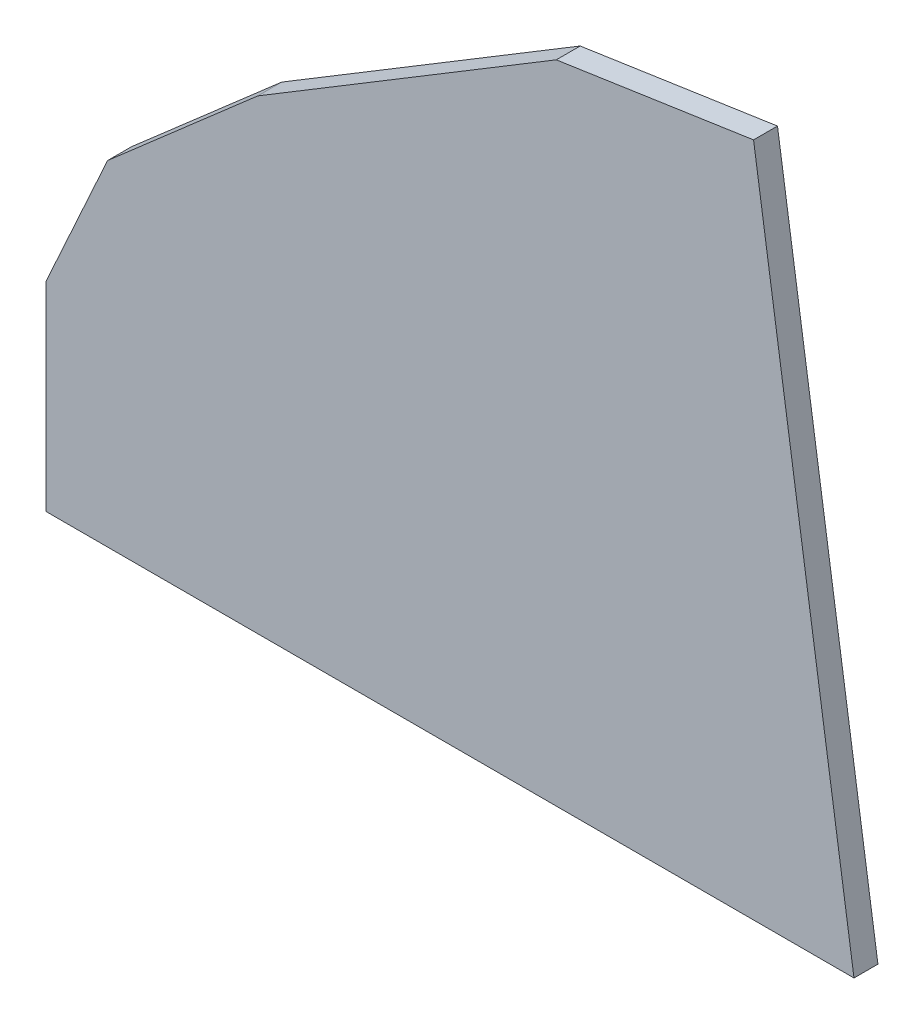
SolidWorks part; units mm, degrees
material "AISI 1020"
ref_plane "Спереди" through (0, 0, 0) normal (0, 0, 1) x (1, 0, 0)
ref_plane "Сверху" through (0, 0, 0) normal (0, 1, 0) x (1, 0, 0)
ref_plane "Справа" through (0, 0, 0) normal (1, 0, 0) x (0, 0, -1)
sketch "Эскиз1" plane through (0, 0, 0) normal (0, 0, 1) x (1, 0, 0)
  line L0 (-207.4146, 166.7802) -> (-245.0885, 133.9065)
  line L1 (-149.1432, 100) -> (-2208.4434, 2460) construction
  line L2 (-215.5022, 100) -> (-2274.8024, 2460) construction
  line L3 (-245.0885, 133.9065) -> (-260.5022, 100)
  line L4 (-115.9638, 100) -> (-4500, 100) construction
  line L5 (-260.5022, 100) -> (-260.5022, 50)
  line L7 (-260.5022, 50) -> (-57.9819, 50)
  line L11 (-57.9819, 50) -> (-83.157, 219.359)
  line L12 (-83.157, 219.359) -> (-132.6136, 212.0073)
  line L13 (-466.7768, 2460) -> (-101.0988, 0) construction
  line L14 (-132.6136, 212.0073) -> (-207.4146, 166.7802)
  line L15 (-245.0885, 133.9065) -> (-215.5022, 100) construction
  line L16 (-215.5022, 100) -> (-260.5022, 100) construction
  line L17 (-132.6136, 212.0073) -> (-115.9638, 100) construction
  line L18 (-115.9638, 100) -> (-207.4146, 166.7802) construction
  line L19 (-20.039, 10) -> (-20.039, 90) construction
  line L20 (-101.0988, 0) -> (-4500, 0) construction
  point P11 (-260.5022, 26.6646)
  point P14 (-73.606, 50)
  point P16 (-57.9819, 50)
  point P17 (0, 0)
  point P18 (-72.1263, 50)
  point P28 (-20.039, 50)
  point P29 (0, 0)
  point P30 (0, 0)
  point P31 (0, 0)
  point P32 (0, 0)
  point P33 (0, 0)
  dimension "D1" = 45
  dimension "D2" = 50
  dimension "D3" = 50
base flange "Базовая кромка1" sketch "Эскиз1" thickness 6 reverse thickness direction no parameters "D1"=0.75
sketch "Сгиб-Линии1" plane through (0, 0, 0) normal (0, 1, 0) x (1, 0, 0)
sketch "Граничная рамка1" plane through (0, 0, 0) normal (0, 1, 0) x (1, 0, 0)
sheet metal parameters "Листовой металл3" thickness 6 parameters "D1"=0.75
flat pattern "Развертка3" [suppressed]
sketch "Сгиб-Линии2" plane through (0, 0, 0) normal (0, 1, 0) x (1, 0, 0)
sketch "Граничная рамка2" [suppressed] plane through (0, 0, 0) normal (0, 1, 0) x (1, 0, 0)
